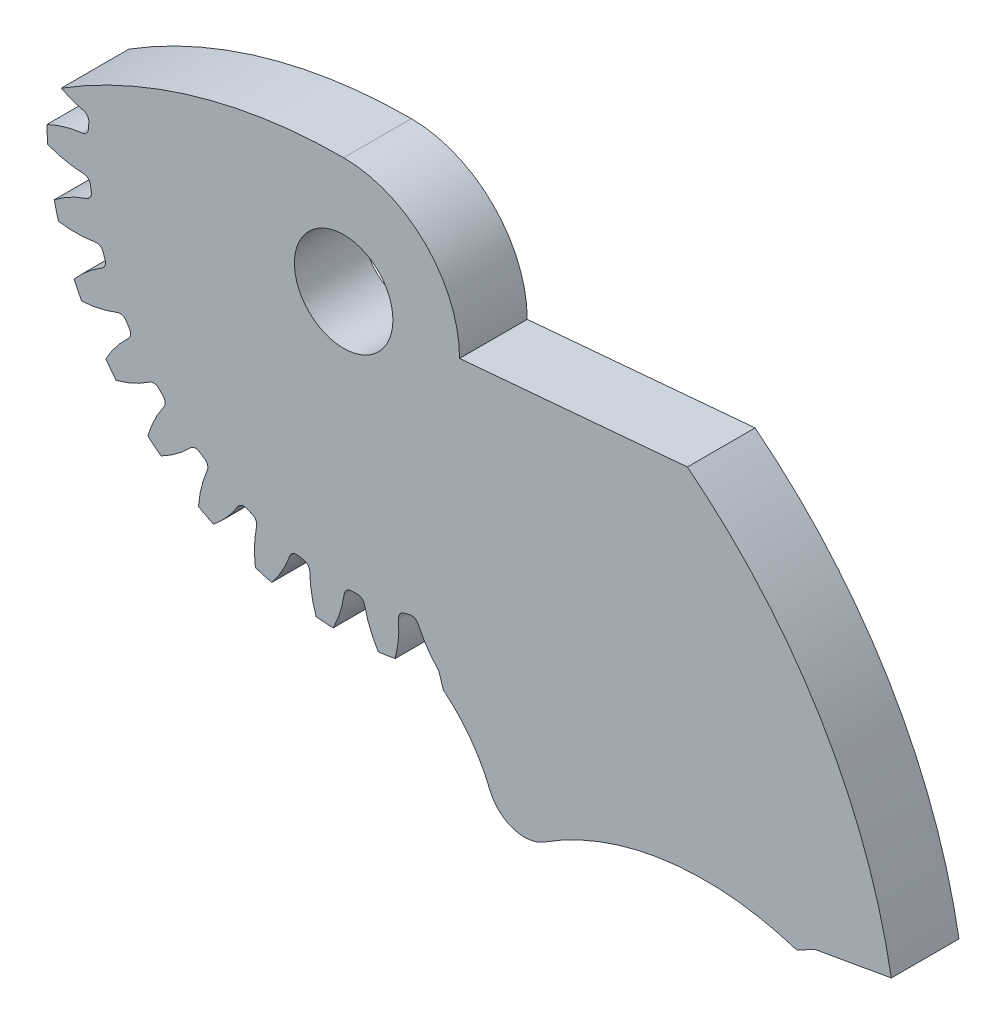
SolidWorks part; units mm, degrees
material "Delrin 2700 NC010, Low Viscosity Acetal Copolymer (SS)"
ref_plane "Front" through (0, 0, 0) normal (0, 0, 1) x (1, 0, 0)
ref_plane "Top" through (0, 0, 0) normal (0, 1, 0) x (1, 0, 0)
ref_plane "Right" through (0, 0, 0) normal (1, 0, 0) x (0, 0, -1)
sketch "Sketch3" plane through (0, 0, 0) normal (0, 0, 1) x (1, 0, 0)
  circle A0 centre (0, 0) radius 40.64
  dimension "od" = 81.28
extrude "gearBody" add sketch "Sketch3" along normal blind 25.4
sketch "Sketch2" plane through (0, 0, 0) normal (0, 0, 1) x (1, 0, 0)
  line L0 (0, 0) -> (34.0786, 14.1158) construction
  line L1 (45.4751, -11.4855) -> (0, 0) construction
  line L2 (0, 0) -> (36.3143, 0) construction
  line L3 (38.0972, -0.458) -> (37.8451, -4.4001) construction
  line L5 (37.9712, -2.4291) -> (0, 0) construction
  line L7 (0, 0) -> (36.8864, 0) construction
  arc A0 (36.879, -0.7403) -> (36.6727, -3.9649) centre (0, 0) ccw construction
  arc A1 (40.637, 0.4947) -> (40.2427, -5.6687) centre (0, 0) ccw construction
  arc A2 (38.0972, -0.458) -> (37.8451, -4.4001) centre (0, 0) ccw construction
  arc A3 (34.9015, -2.6404) -> (34.9534, -1.8283) centre (0, 0) ccw
  arc A4 (45.4751, -11.4855) -> (35.6466, -3.6712) centre (32.0022, -18.3431) ccw
  arc A5 (45.4751, -11.4855) -> (46.5679, 5.5974) centre (0, 0) ccw
  arc A6 (46.5679, 5.5974) -> (35.8238, -0.9008) centre (34.0786, 14.1158) cw
  arc A7 (34.9534, -1.8283) -> (35.8238, -0.9008) centre (35.9376, -1.8798) cw
  arc A8 (35.6466, -3.6712) -> (34.9015, -2.6404) centre (35.8842, -2.7147) cw
  point P6 (46.5679, 5.5974)
  point P22 (45.4751, -11.4855)
  dimension "baseDia" = 73.7729
  dimension "od" = 81.28
  dimension "pd" = 76.2
  dimension "rd" = 70.0024
  dimension "rFillet" = 0.9855
  dimension "pointX" = 46.5679
  dimension "pointY" = 5.5974
  dimension "CTT" = 3.9421
  dimension "flankCenterAngle" = 22.5
extrude "toothCut" cut sketch "Sketch2" along normal through all
pattern_circular "CirPattern1" count 30 over 360 about axis through (0, 0, 25.4) along (0, 0, -1) of "toothCut"
sketch "hub1Dia" plane through (0, 0, 0) normal (0, 0, -1) x (-1, 0, 0)
  circle A0 centre (0, 0) radius 12.7
  dimension "hub1Dia" = 25.4
sketch "hub2Dia" plane through (0, 0, 25.4) normal (0, 0, 1) x (1, 0, 0)
  circle A0 centre (0, 0) radius 12.7
  dimension "hub2dia" = 25.4
sketch "boreDia" plane through (0, 0, 0) normal (0, 0, 1) x (1, 0, 0)
  circle A0 centre (0, 0) radius 9.525
  dimension "boreDia" = 19.05
extrude "bore" cut sketch "boreDia" against normal mid plane 25400
sketch "Sketch4" plane through (0, 0, 25.4) normal (0, 0, 1) x (1, 0, 0)
  circle A0 centre (0, -57.15) radius 76.1746
  arc A2 (-41.7195, 6.5842) -> (41.7195, 6.5842) centre (0, 0) cw
  dimension "D1" = 152.3492
  dimension "D2" = 57.15
extrude "Cut-Extrude1" cut sketch "Sketch4" against normal through all contours A0 region at (0, 26.0638, 25.4)
sketch "Sketch5" plane through (0, 0, 25.4) normal (0, 0, 1) x (1, 0, 0)
  line L0 (0, 19.0246) -> (21.5163, 0.2011)
  line L1 (21.5163, 0.2011) -> (8.9608, -26.928)
  line L2 (8.9608, -26.928) -> (13.028, -38.4952)
  line L3 (0, 0) -> (0, -57.15) construction
  line L4 (0, -57.15) -> (-48.0548, 1.9542) construction
  line L5 (0, -57.15) -> (65.9691, -95.2373) construction
  line L6 (13.6543, -40.4261) -> (13.028, -38.4952)
  line L9 (0, -57.15) -> (75.0173, -43.9224) construction
  line L10 (75.0173, -43.9224) -> (64.5114, -45.7749)
  line L11 (64.5114, -45.7749) -> (62.0894, -47.0863)
  circle A1 centre (0, -57.15) radius 76.1746 construction
  arc A4 (33.1977, 11.4101) -> (-34.0662, 10.9827) centre (0, -57.15) ccw construction
  arc A5 (0, 19.0246) -> (75.0173, -43.9224) centre (0, -57.15) cw
  circle A6 centre (0, -57.15) radius 21.59 construction
  arc A9 (33.1977, 11.4101) -> (-34.0662, 10.9827) centre (0, -57.15) ccw construction
  arc A10 (20.0525, -49.1485) -> (13.6543, -40.4261) centre (0, -57.15) ccw
  circle A12 centre (49.4934, -85.725) radius 40.64 construction
  arc A13 (27.5177, -51.539) -> (62.0894, -47.0863) centre (49.4934, -85.725) cw
  arc A14 (27.5177, -51.539) -> (20.0525, -49.1485) centre (24.7708, -47.2658) cw
  point P28 (21.569, -56.1981)
  dimension "D1" = 43.18
  dimension "D3" = 81.28
  dimension "D7" = 5.08
  dimension "D2" = 120
  dimension "D4" = 57.15
  dimension "D6" = 10.668
  dimension "D5" = 80
extrude "Boss-Extrude1" add sketch "Sketch5" against normal up to surface (25.4 mm away) up to face at (9.525, 0, 0)
sketch "Sketch6" plane through (0, 0, 0) normal (0, 1, 0) x (1, 0, 0)
  line L0 (-46.1384, -9.271) -> (97.8162, -9.271)
  line L4 (97.8162, -9.271) -> (71.9328, -41.1538)
  line L5 (71.9328, -41.1538) -> (-48.6783, -38.0647)
  line L6 (-48.6783, -38.0647) -> (-46.1384, -9.271)
  dimension "D1" = 9.271
extrude "Cut-Extrude2" cut sketch "Sketch6" against normal through all both and the other way through all
sketch "Sketch7" plane through (0, 0, 9.271) normal (0, 0, 1) x (1, 0, 0)
  line L8 (15.875, 0) -> (50.2154, 3.0044)
  line L9 (-43.0106, 8.3498) -> (-40.0828, 3.8911)
  line L10 (0, -57.15) -> (-43.0106, 8.3498) construction
  line L11 (0, 0) -> (80.4469, 0) construction
  arc A0 (-40.2427, 5.6687) -> (-35.6466, 3.6712) centre (-32.0022, 18.3431) ccw construction
  circle A3 centre (0, -57.15) radius 73.025 construction
  circle A4 centre (0, 0) radius 15.875 construction
  arc A5 (0, 15.875) -> (15.875, 0) centre (0, 0) cw
  circle A8 centre (0, -57.15) radius 78.359 construction
  arc A9 (-43.0106, 8.3498) -> (50.2154, 3.0044) centre (0, -57.15) cw
  arc A10 (0, 15.875) -> (-40.0828, 3.8911) centre (0, -57.15) ccw
  point P0 (-36.4485, 3.894)
  dimension "D2" = 57.15
  dimension "D1" = 146.05
  dimension "D3" = 156.718
  dimension "D4" = 5
extrude "Cut-Extrude3" cut sketch "Sketch7" against normal through all both
sketch "Sketch8" plane through (0, 0, 9.271) normal (0, 0, 1) x (1, 0, 0)
  circle A0 centre (0, 0) radius 6.7469
  circle A1 centre (0, 0) radius 10.9012
  dimension "D1" = 13.4937
extrude "Boss-Extrude2" add sketch "Sketch8" against normal up to surface (9.271 mm away) up to face at (9.525, 0, 0)
equation "\"Bodytube_OD\" = 6.17in"
equation "\"Bodytube_ID\" = 5.998in"
equation "\"Fwd_Tube_Length\" = 38in"
equation "\"Mid_Tube_Length\" = 8in"
equation "\"Aft_Section_Length\"= 40in"
equation "\"Mid_Coupler_Length\" = 13in"
equation "\"Aft_Lower_Length\"= 22in"
equation "\"AB_Coupler_OD_Length\"= 1in"
equation "\"AB_Coupling_Section_Length\"= 0.375in"
equation "\"AB_Coupler_Length\"= \"AB_Coupler_OD_Length\" + \"AB_Coupling_Section_Length\" * 2"
equation "\"Cutout_Angle\" = 80"
equation "\"AB_Paddle_Height\" = 0.375in"
equation "\"AB_Coupler_Num_Screws\"= 6"
equation "\"Num_Cutouts\" = 3"
equation "\"AB_Coupler_OD\"= 6.17in"
equation "\"AB_Coupler_ID\"= 5.75in"
equation "\"AB_Coupler_Surface_Diameter\"= 5.998in"
equation "\"AB_Coupling_Screw_Diameter\"= 0.1065in"
equation "\"AB_Central_Bushing_Length\" = .75in"
equation "\"Lead_Screw_Dist\" = 2.25in"
equation "\"Lead_Screw_Diam\" = (27/64)*1in"
equation "\"Lead_Screw_Length\" = (\"Mid_Coupler_Length\" + 2*0.375in + 2*0.5in)"
equation "\"Paddle_Pin_Offset\" = .25in"
equation "\"Paddle_Pin_Radius\" = 2.25in"
equation "\"Fwd_BKHD_From_Top\" = 18in"
equation "\"D1@Sketch4\"=\"Bodytube_ID\""
equation "\"D2@Sketch4\"=\"Paddle_Pin_Radius\""
equation "\"D3@Sketch5\"=\"Paddle_Gear_OD\""
equation "\"D4@Sketch5\"=\"Paddle_Pin_Radius\""
equation "\"Motor_OD\" = 4in"
equation "\"Aft_Upper_Length\"= \"Aft_Section_Length\" - \"Aft_Lower_Length\" - \"AB_Coupler_OD_Length\""
equation "\"Paddle_Gear_OD\" = 3.2in"
equation "\"D5@Sketch5\"=\"Cutout_Angle\""
equation "\"D6@Sketch5\"=\"AB_Coupler_OD\"-\"AB_Coupler_ID\""
equation "\"D1@Sketch7\"=\"AB_Coupler_ID\""
equation "\"D2@Sketch7\"=\"Paddle_Pin_Radius\""
equation "\"D3@Sketch7\"=\"Bodytube_OD\""
